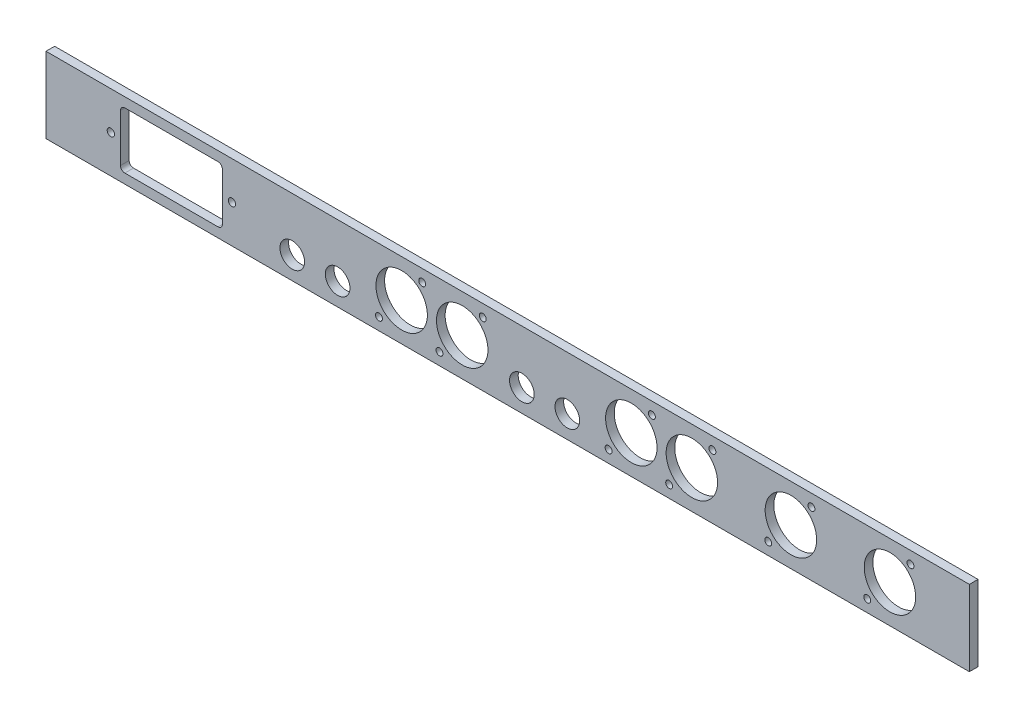
SolidWorks part; units mm, degrees
ref_plane "Front Plane" through (0, 0, 0) normal (0, 0, 1) x (1, 0, 0)
ref_plane "Top Plane" through (0, 0, 0) normal (0, 1, 0) x (1, 0, 0)
ref_plane "Right Plane" through (0, 0, 0) normal (1, 0, 0) x (0, 0, -1)
sketch "Sketch1" plane through (0, 0, 0) normal (0, 0, 1) x (1, 0, 0)
  line L0 (0, 17.5) -> (0, -17.5) construction
  line L1 (-213.5, -17.5) -> (213.5, -17.5)
  line L2 (-213.5, -17.5) -> (-213.5, 17.5)
  line L3 (-213.5, 17.5) -> (213.5, 17.5)
  line L4 (213.5, -17.5) -> (213.5, 17.5)
  line L5 (0, 0) -> (-213.5, 0) construction
  point P8 (0, 0)
  dimension "D1" = 427
  dimension "D2" = 35
extrude "Boss-Extrude1" add sketch "Sketch1" along normal blind 4
sketch "Sketch2" plane through (0, 0, 4) normal (0, 0, 1) x (1, 0, 0)
  line L0 (-213.5, 0) -> (213.5, 0) construction
  line L1 (-213.5, 17.5) -> (-213.5, -17.5) construction
  line L2 (213.5, -17.5) -> (213.5, 17.5) construction
  line L3 (-21.0232, 11.9) -> (-21.0232, -11.9) construction
  line L4 (-49.0232, 11.9) -> (-49.0232, -11.9) construction
  line L5 (-21.0232, 11.9) -> (-11.5163, 11.9) construction
  line L6 (-49.0232, 11.9) -> (-39.5163, 11.9) construction
  line L7 (-5.4186, 0) -> (-5.4186, 17.5) construction
  line L8 (-115.5, 0) -> (-115.5, 17.5) construction
  line L9 (51.2245, 11.9) -> (60.7313, 11.9) construction
  line L10 (-24.19, 0) -> (-24.19, 4.5526) construction
  line L11 (-24.19, 0) -> (-24.19, 17.5) construction
  line L12 (213.5, 17.5) -> (-213.5, 17.5) construction
  line L14 (-213.5, -17.5) -> (213.5, -17.5) construction
  line L17 (121.8577, 0) -> (121.8577, 4.5526) construction
  line L18 (125.0245, 11.9) -> (134.5313, 11.9) construction
  line L19 (125.0245, 11.9) -> (125.0245, -11.9) construction
  line L20 (51.2245, 11.9) -> (51.2245, -11.9) construction
  line L21 (76.0577, 0) -> (76.0577, 4.5526) construction
  line L22 (79.2245, 11.9) -> (88.7313, 11.9) construction
  line L23 (-21.0232, 0) -> (-21.0232, 17.5) construction
  line L24 (79.2245, 11.9) -> (79.2245, -11.9) construction
  line L25 (-200.5, 17.5) -> (-200.5, -17.5) construction
  line L26 (-213.5, -17.5) -> (213.5, -17.5) construction
  line L27 (-213.5, 17.5) -> (-213.5, -17.5) construction
  line L28 (200.5, -17.5) -> (200.5, 17.5) construction
  line L29 (213.5, -17.5) -> (213.5, 17.5) construction
  line L30 (167.6577, 0) -> (167.6577, 4.5526) construction
  line L31 (-155.5, 0) -> (-155.5, 13.05) construction
  line L32 (-179.05, -13.05) -> (-131.95, 13.05) construction
  line L33 (-179.05, 13.05) -> (-131.95, -13.05) construction
  line L34 (-177.05, -13.05) -> (-133.95, -13.05)
  line L35 (-179.05, -11.05) -> (-179.05, 11.05)
  line L36 (-177.05, 13.05) -> (-133.95, 13.05)
  line L37 (-131.95, -11.05) -> (-131.95, 11.05)
  line L38 (170.8245, 11.9) -> (180.3313, 11.9) construction
  line L39 (170.8245, 11.9) -> (170.8245, -11.9) construction
  circle A0 centre (-21.0232, 0) radius 11.9
  circle A1 centre (-31.5163, -11.9) radius 1.6
  circle A2 centre (-11.5163, 11.9) radius 1.6
  circle A3 centre (-59.5163, -11.9) radius 1.6
  circle A4 centre (-49.0232, 0) radius 11.9
  circle A5 centre (-39.5163, 11.9) radius 1.6
  circle A6 centre (120.4813, -11.9) radius 1.6
  circle A7 centre (140.4813, 11.9) radius 1.6
  circle A8 centre (130.9745, 0) radius 11.9
  circle A9 centre (166.2813, -11.9) radius 1.6
  circle A10 centre (186.2813, 11.9) radius 1.6
  circle A11 centre (176.7745, 0) radius 11.9
  circle A12 centre (-78.6232, -7.125) radius 5.7
  circle A13 centre (-99.6232, -7.125) radius 5.7
  circle A14 centre (27.5745, -7.125) radius 5.7
  circle A15 centre (74.6813, -11.9) radius 1.6
  circle A16 centre (94.6813, 11.9) radius 1.6
  circle A17 centre (57.1745, 0) radius 11.9
  circle A18 centre (85.1745, 0) radius 11.9
  circle A19 centre (6.5745, -7.125) radius 5.7
  circle A20 centre (66.6813, 11.9) radius 1.6
  circle A21 centre (46.6813, -11.9) radius 1.6
  circle A22 centre (-127.5, 0) radius 1.7
  arc A23 (-131.95, -11.05) -> (-133.95, -13.05) centre (-133.95, -11.05) cw
  arc A24 (-179.05, -11.05) -> (-177.05, -13.05) centre (-177.05, -11.05) ccw
  arc A25 (-177.05, 13.05) -> (-179.05, 11.05) centre (-177.05, 11.05) ccw
  arc A26 (-133.95, 13.05) -> (-131.95, 11.05) centre (-133.95, 11.05) cw
  circle A27 centre (-183.5, 0) radius 1.7
  point P14 (91.1245, 0)
  point P27 (-60.9232, 0)
  point P32 (-9.1232, 0)
  point P42 (-105.3232, -7.125)
  point P48 (0.8768, 0)
  point P49 (0.8752, -7.0363)
  point P50 (9.5246, 22.4841)
  point P52 (0.8768, 0)
  point P54 (136.9245, 0)
  point P77 (39.3245, 0)
  point P123 (182.7245, 0)
  dimension "D3" = 3.2
  dimension "D4" = 11.4
  dimension "D1" = 23.8
  dimension "D2" = 3.2
  dimension "D6" = 11.4
  dimension "D9" = 13
  dimension "D11" = 113.8768
  dimension "D5" = 23.8
  dimension "D7" = 21
  dimension "D8" = 28
  dimension "D10" = 13
  dimension "D13" = 153.9837
  dimension "D14" = 164.4768
  dimension "D15" = 173.9837
  dimension "D16" = 181.9837
  dimension "D17" = 201.9837
  dimension "D18" = 427
  dimension "D19" = 5.6
  dimension "D20" = 10.375
  dimension "D21" = 17.5
  dimension "D23" = 3
extrude "Cut-Extrude1" cut sketch "Sketch2" against normal blind 4
